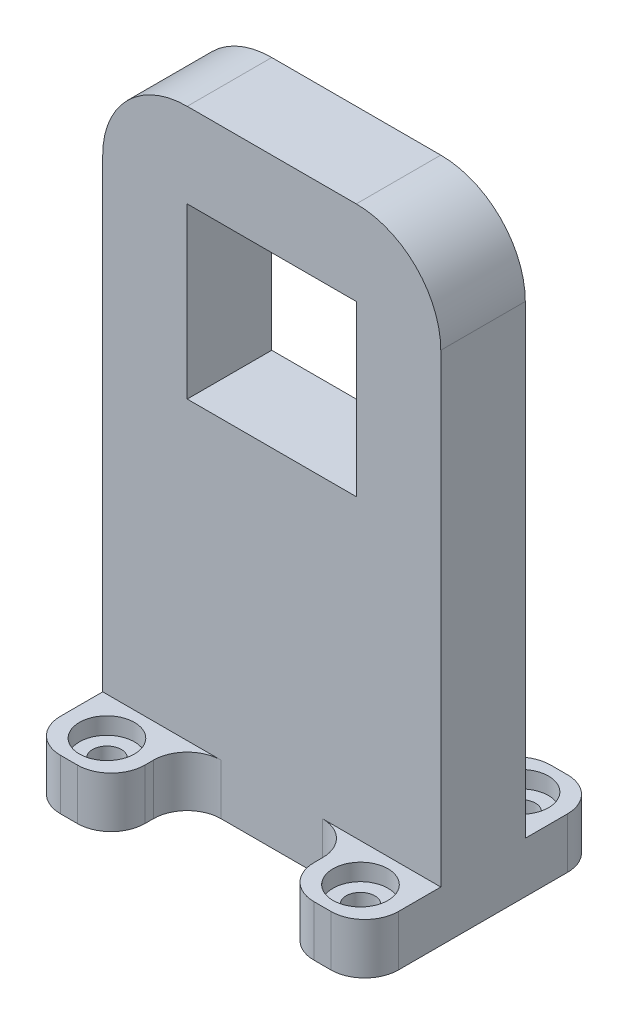
SolidWorks part; units mm, degrees
ref_plane "Plan de face" through (0, 0, 0) normal (0, 0, 1) x (1, 0, 0)
ref_plane "Plan de dessus" through (0, 0, 0) normal (0, 1, 0) x (1, 0, 0)
ref_plane "Plan de droite" through (0, 0, 0) normal (1, 0, 0) x (0, 0, -1)
sketch "Esquisse1" plane through (0, 0, 0) normal (0, 0, 1) x (1, 0, 0)
  line L0 (0, 0) -> (40, 0)
  line L1 (0, 0) -> (40, 0) construction
  line L2 (0, 0) -> (0, 71) construction
  line L3 (0, 71) -> (40, 71) construction
  line L4 (40, 0) -> (40, 71) construction
  line L5 (40, 0) -> (40, 71)
  line L6 (40, 71) -> (0, 71)
  line L7 (0, 71) -> (0, 0)
  line L9 (10, 61) -> (30, 61)
  line L10 (10, 61) -> (10, 41)
  line L11 (10, 41) -> (30, 41)
  line L12 (30, 61) -> (30, 41)
  dimension "D1" = 40
  dimension "D2" = 71
  dimension "D3" = 10
  dimension "D4" = 10
  dimension "D5" = 10
  dimension "D6" = 41
extrude "Boss.-Extru.1" add sketch "Esquisse1" along normal blind 10
sketch "Esquisse3" plane through (0, 0, 10) normal (0, 0, 1) x (1, 0, 0)
  line L0 (30, 0) -> (40, 0)
  line L3 (0, 6) -> (10, 6)
  line L4 (0, 71) -> (0, 0)
  line L5 (0, 0) -> (40, 0)
  line L6 (40, 0) -> (40, 71)
  line L7 (40, 71) -> (0, 71)
  line L8 (0, 6) -> (0, 0)
  line L9 (0, 0) -> (10, 0)
  line L12 (10, 0) -> (10, 6)
  line L14 (40, 0) -> (40, 6)
  line L15 (40, 6) -> (30, 6)
  line L16 (30, 0) -> (30, 6)
  line L17 (0, 0) -> (40, 0) construction
  dimension "D4" = 10
  dimension "D2" = 10
  dimension "D3" = 6
  dimension "D5" = 6
extrude "Boss.-Extru.2" add sketch "Esquisse3" along normal blind 9
sketch "Esquisse4" plane through (0, 6, 0) normal (0, 1, 0) x (1, 0, 0)
  line L0 (0, -19) -> (0, -10) construction
  line L1 (10, -10) -> (0, -10) construction
  line L2 (40, -19) -> (40, -10) construction
  line L3 (40, -10) -> (0, -10) construction
  circle A0 centre (5, -14.5) radius 1.5
  circle A1 centre (35, -14.5) radius 1.5
  dimension "D3" = 3
  dimension "D4" = 3
  dimension "D1" = 5
  dimension "D2" = 4.5
  dimension "D5" = 5
  dimension "D6" = 4.5
hole_wizard "Chambrage pour tête cylindrique fendue M31" positions "Esquisse5" profile "Esquisse6" counterbore size "M3" standard "ISO" end condition through all
sketch "Esquisse5" plane through (0, 6, 0) normal (0, 1, 0) x (1, 0, 0)
  point P0 (5, -14.5)
  point P3 (35, -14.5)
sketch "Esquisse6" plane through (5, 6, 14.5) normal (1, 0, 0) x (0, 0, 1)
  line L0 (0, 0) -> (0, 6)
  line L1 (0, 6) -> (1.7, 6)
  line L3 (1.7, 6) -> (1.7, 2)
  line L4 (1.7, 2) -> (3.25, 2)
  line L5 (3.25, 2) -> (3.25, 0)
  line L7 (3.25, 0) -> (0, 0)
  line L11 (0, -6.35) -> (0, 107.95) construction
  dimension "Diamètre du perçage jusqu'au prochain" = 3.4
  dimension "Profondeur du perçage jusqu'au prochain" = 6
  dimension "Diamètre du chambrage" = 6.5
  dimension "Profondeur du chambrage" = 2
ref_plane "Plan1" through (0, 0, 5) normal (0, 0, 1) x (1, 0, 0)
mirror "Symétrie1" about plane through (0, 0, 5) normal (0, 0, 1) of "Chambrage pour tête cylindrique fendue M31", "Boss.-Extru.2"
fillet "Congé1" radius 4 12 edges at (40, 3, 19) (30, 3, 19) (0, 3, 19) (10, 3, 19) (30, 3, 10) (10, 3, 10) (0, 3, -9) (10, 3, -9) (10, 3, 0) (30, 3, 0) (30, 3, -9) (40, 3, -9)
fillet "Congé2" radius 10 2 edges at (0, 71, 5) (40, 71, 5)
equation "\"largeur_cremail\"= 20"
equation "\"hauteur_cremail\"= 20"
equation "\"epaiss_cadre\"= 10"
equation "\"hauteur_basecremail_sol\"= 122 - 76 - 15"
equation "\"D1@Esquisse1\"=\"largeur_cremail\"+\"epaiss_cadre\"*2"
equation "\"D2@Esquisse1\"=\"hauteur_basecremail_sol\"+\"hauteur_cremail\"+\"epaiss_cadre\"*2"
equation "\"D3@Esquisse1\"=\"epaiss_cadre\""
equation "\"D4@Esquisse1\"=\"epaiss_cadre\""
equation "\"D5@Esquisse1\"=\"epaiss_cadre\""
equation "\"D6@Esquisse1\"=\"hauteur_basecremail_sol\"+\"epaiss_cadre\""
equation "\"D1@Boss.-Extru.1\"=\"epaiss_cadre\""
equation "\"D2@Esquisse3\"=\"epaiss_cadre\""
equation "\"D4@Esquisse3\"=\"epaiss_cadre\""
equation "\"D5@Esquisse3\"=\"D3@Esquisse3\""
equation "\"D1@Esquisse4\"=\"epaiss_cadre\"/2"
equation "\"D5@Esquisse4\"=\"epaiss_cadre\"/2"
equation "\"D6@Esquisse4\"=4.5"
